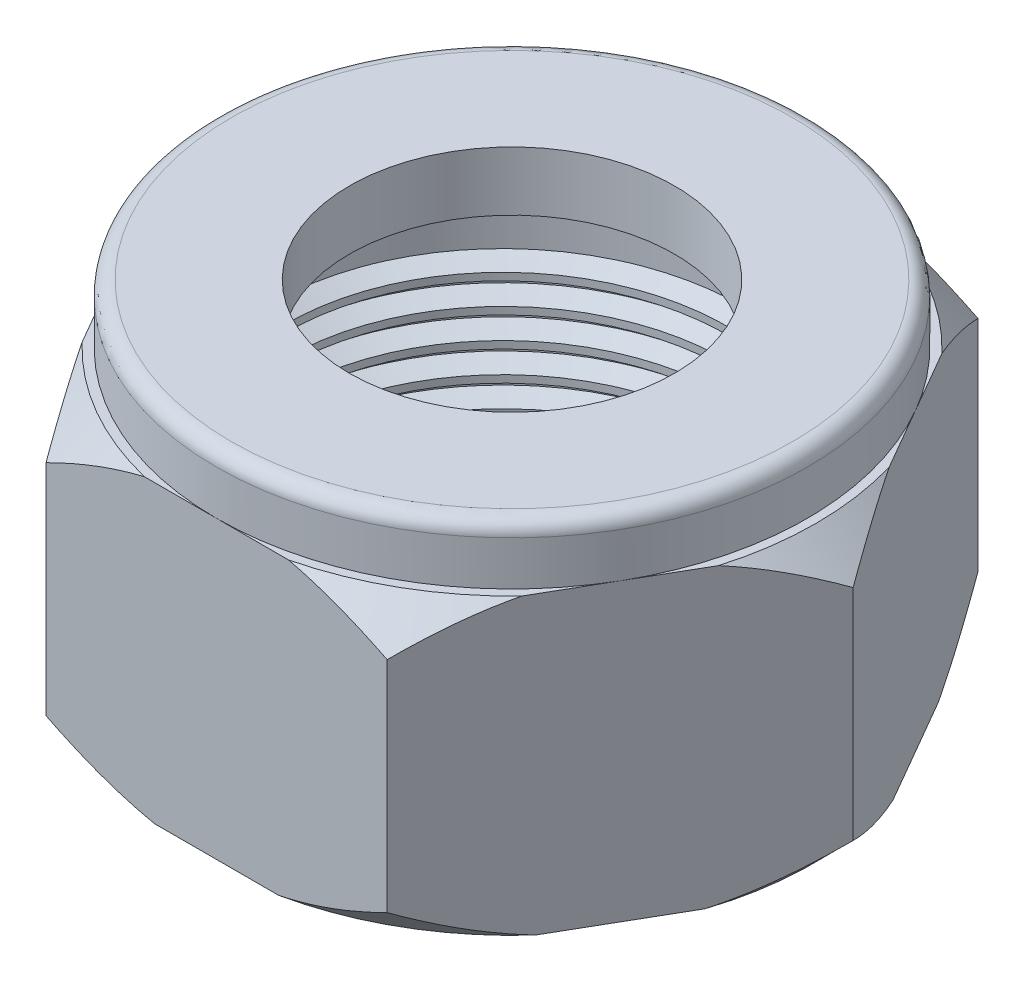
SolidWorks part; units mm, degrees
material "Free-Cutting Brass, UNS C36000"
ref_plane "Front Plane" through (0, 0, 0) normal (0, 0, 1) x (1, 0, 0)
ref_plane "Top Plane" through (0, 0, 0) normal (0, 1, 0) x (1, 0, 0)
ref_plane "Right Plane" through (0, 0, 0) normal (1, 0, 0) x (0, 0, -1)
sketch "Sketch1" plane through (0, 0, 0) normal (0, 1, 0) x (1, 0, 0)
  line L1 (-11.547, 0) -> (-5.7735, -10)
  line L2 (-5.7735, -10) -> (5.7735, -10)
  line L3 (5.7735, -10) -> (11.547, 0)
  line L4 (11.547, 0) -> (5.7735, 10)
  line L5 (5.7735, 10) -> (-5.7735, 10)
  line L6 (-5.7735, 10) -> (-11.547, 0)
  circle A0 centre (0, 0) radius 10 construction
  circle A1 centre (0, 0) radius 8
  dimension "D1" = 20
extrude "Boss-Extrude1" add sketch "Sketch1" along normal mid plane 10
sketch "Sketch2" plane through (0, 0, 0) normal (0, 0, 1) x (1, 0, 0)
  line L0 (12.3313, 2.9615) -> (9.5689, 5.7239)
  line L1 (9.5689, 5.7239) -> (12.3313, 5.7239)
  line L2 (12.3313, 5.7239) -> (12.3313, 2.9615)
  line L3 (9.5689, -5.6493) -> (12.3313, -2.8868)
  line L4 (12.3313, -2.8868) -> (12.3313, -5.6493)
  line L5 (12.3313, -5.6493) -> (9.5689, -5.6493)
  line L6 (0, 0) -> (0, 2.5758) construction
  point P3 (10.9501, 4.3427)
  point P7 (10.9501, -4.268)
revolve "Cut-Revolve1" cut sketch "Sketch2" angle 360 about L6
sketch "Sketch3" plane through (0, 5, 0) normal (0, 1, 0) x (1, 0, 0)
  circle A0 centre (0, 0) radius 10
  circle A1 centre (0, 0) radius 5.5
  dimension "D1" = 11
extrude "Boss-Extrude2" add sketch "Sketch3" along normal blind 2
thread "Thread1" pitch 1 method extrude profile "Thread Profile1" start angle 0, offset 0, length 7, pitch 1, diameter 16
ref_plane "Plane1" through (8, -5, 0) normal (0, 0, 1) x (1, 0, 0)
sketch "Thread Profile1" plane through (8, -5, 0) normal (0, 0, 1) x (1, 0, 0)
  line L0 (0, 0) -> (0, 1) construction
  line L11 (0, 0) -> (0, 0.875)
  line L12 (0, 0.875) -> (-0.5413, 0.5625)
  line L13 (-0.5413, 0.5625) -> (-0.5413, 0.3125)
  line L15 (-0.5413, 0.3125) -> (0, 0)
  line L17 (-0.5413, 0.4375) -> (0, 0.4375) construction
  point P2 (0, 0)
  dimension "Pitch" = 1
  dimension "Profile_Angle" = 60
  dimension "Profile_Land" = 0.25
  dimension "Profile_Height" = 0.5413
fillet "Fillet1" radius 0.5 1 edges at (0, 7, 10)
ref_axis "Axis1" through (0, 13.7004, 0) along (0, -1, 0)
